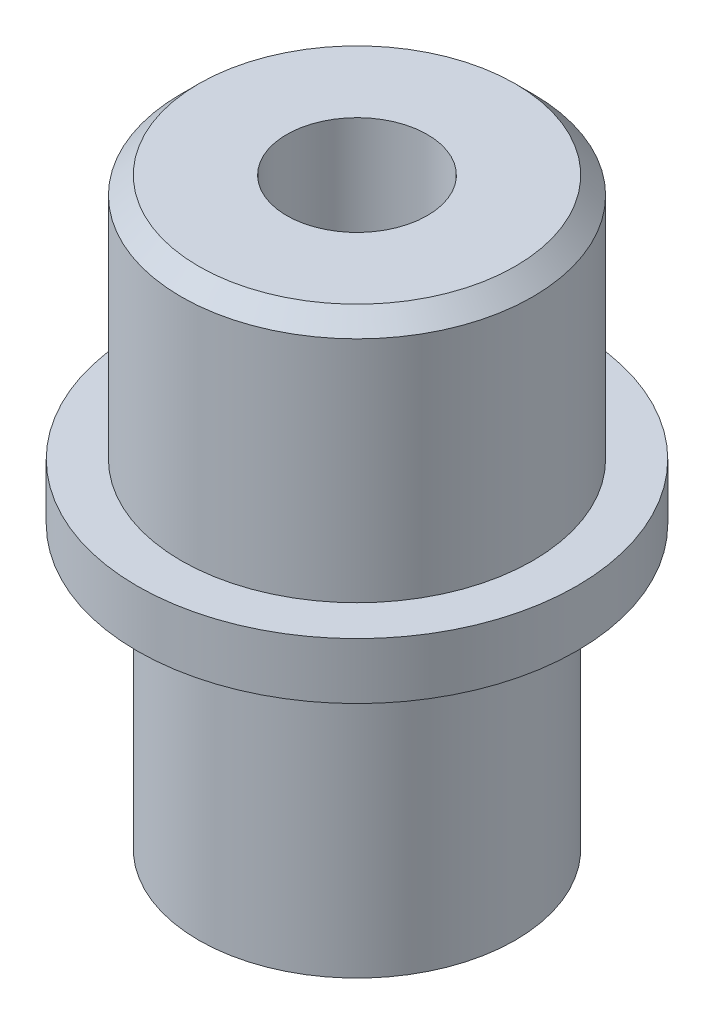
SolidWorks part; units mm, degrees
ref_plane "Front Plane" through (0, 0, 0) normal (0, 0, 1) x (1, 0, 0)
ref_plane "Top Plane" through (0, 0, 0) normal (0, 1, 0) x (1, 0, 0)
ref_plane "Right Plane" through (0, 0, 0) normal (1, 0, 0) x (0, 0, -1)
sketch "Sketch1" plane through (0, 0, 0) normal (0, 0, 1) x (1, 0, 0)
  line L0 (0, 0) -> (0, 7.9688) construction
  line L1 (-2.54, 13.0488) -> (-6.35, 13.0488)
  line L2 (-6.35, 13.0488) -> (-6.35, 4.1588)
  line L3 (-6.35, 4.1588) -> (-7.9375, 4.1588)
  line L4 (-7.9375, 4.1588) -> (-7.9375, 2.1268)
  line L5 (-7.9375, 2.1268) -> (-5.715, 2.1268)
  line L6 (-5.715, 2.1268) -> (-5.715, -8.0332)
  line L7 (-5.715, -8.0332) -> (0, -8.0332)
  line L8 (0, -8.0332) -> (0, 7.9688)
  line L9 (-2.54, 13.0488) -> (-2.54, 7.9688)
  line L10 (-2.54, 7.9688) -> (0, 7.9688)
  dimension "D1" = 6.35
  dimension "D2" = 8.89
  dimension "D3" = 2.032
  dimension "D4" = 7.9375
  dimension "D5" = 10.16
  dimension "D6" = 5.715
  dimension "D7" = 2.54
  dimension "D8" = 5.08
revolve "Revolve1" add sketch "Sketch1" angle 360 about L0
chamfer "Chamfer1" distance 0.635 angle 45 1 edges at (6.35, 13.0488, 0)
ref_axis "Axis1" through (0, 12.4138, 0) along (0, -1, 0)
